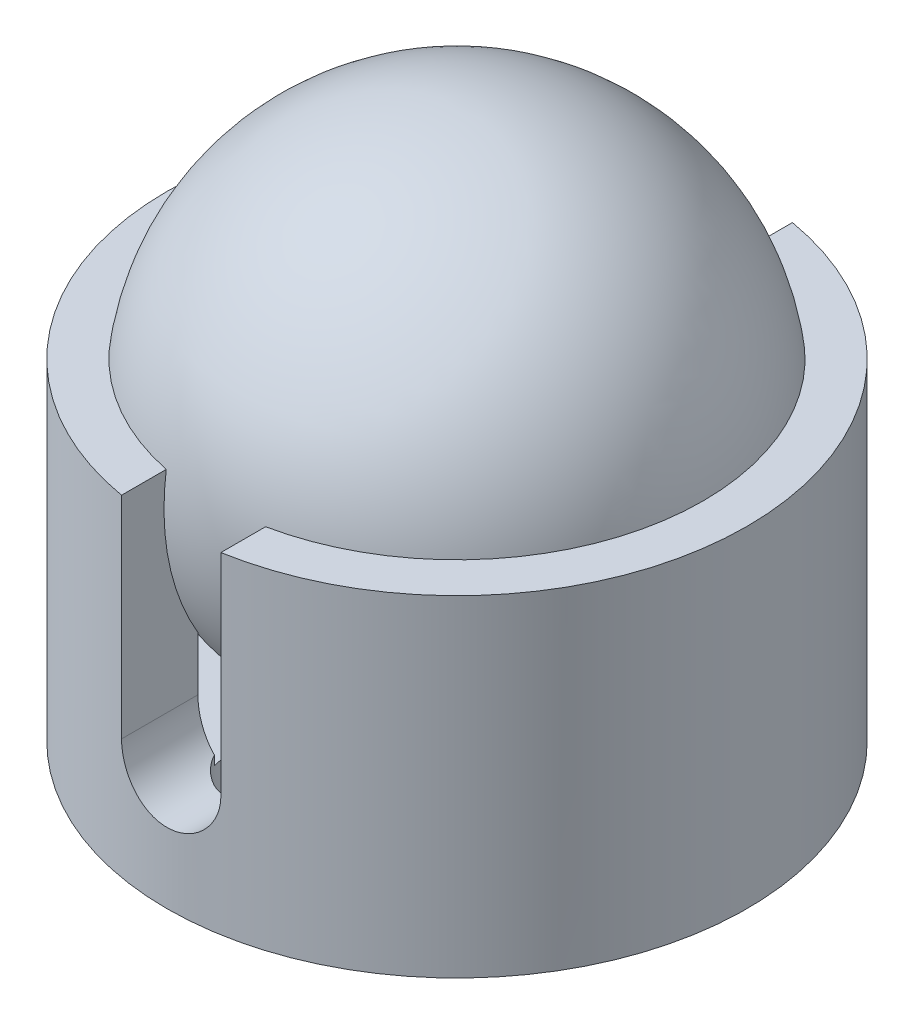
SolidWorks part; units mm, degrees
ref_plane "Front Plane" through (0, 0, 0) normal (0, 0, 1) x (1, 0, 0)
ref_plane "Top Plane" through (0, 0, 0) normal (0, 1, 0) x (1, 0, 0)
ref_plane "Right Plane" through (0, 0, 0) normal (1, 0, 0) x (0, 0, -1)
sketch "Sketch1" plane through (0, 0, 0) normal (0, 1, 0) x (1, 0, 0)
  circle A0 centre (0, 0) radius 11.1252
  dimension "D1" = 22.2504
extrude "Boss-Extrude1" add sketch "Sketch1" along normal blind 12.7
sketch "Sketch2" plane through (0, 0, 0) normal (0, 0, 1) x (1, 0, 0)
  line L1 (0, 20.955) -> (0, 1.905)
  arc A0 (0, 1.905) -> (0, 20.955) centre (0, 11.43) ccw
  point P1 (0, 0)
  point P4 (0, 20.955)
  dimension "D1" = 19.05
  dimension "D2" = 20.955
ref_axis "Axis1" through (0, 22.0027, 0) along (0, -1, 0)
ref_plane "Plane1" through (0, 0, -11.1252) normal (0, 0, -1) x (-1, 0, 0)
sketch "Sketch4" plane through (0, 12.7, 0) normal (0, 1, 0) x (1, 0, 0)
  circle A0 centre (0, 0) radius 8.255
  dimension "D1" = 16.51
extrude "Cut-Extrude2" cut sketch "Sketch4" against normal blind 10 contours A0
sketch "Sketch3" plane through (0, 0, -11.1252) normal (0, 0, -1) x (-1, 0, 0)
  line L0 (-1.905, 12.7) -> (-1.905, 4.605)
  line L1 (1.905, 12.7) -> (-1.905, 12.7)
  line L2 (1.905, 12.7) -> (1.905, 4.605)
  line L3 (0, 22.0027) -> (0, -1.0478) construction
  line L4 (11.1252, 12.7) -> (-11.1252, 12.7) construction
  line L6 (8.255, 2.7) -> (-8.255, 2.7) construction
  arc A0 (-1.905, 4.605) -> (1.905, 4.605) centre (0, 4.605) ccw
  point P4 (0, 0)
  point P12 (0, 2.7)
  dimension "D1" = 3.81
extrude "Cut-Extrude1" cut sketch "Sketch3" against normal through all
revolve "Revolve3" add sketch "Sketch2" angle 360 about L1
sketch "Sketch5" plane through (0, 0, 0) normal (0, -1, 0) x (1, 0, 0)
  circle A0 centre (0, 7.747) radius 1.2065
  circle A1 centre (0, -7.747) radius 1.2065
  point P5 (0, 0)
  dimension "D3" = 2.413
  dimension "D1" = 15.494
  dimension "D2" = 7.747
extrude "Cut-Extrude3" cut sketch "Sketch5" against normal up to next
